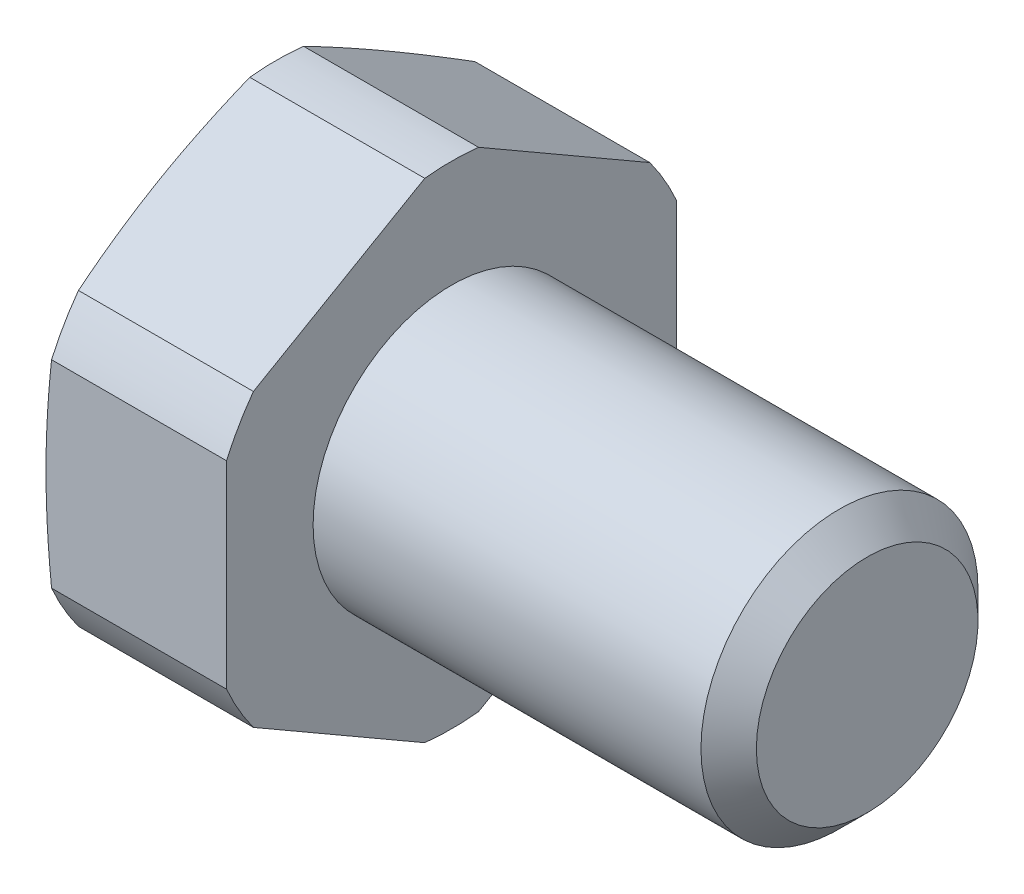
SolidWorks part; units mm, degrees
material "AISI 1020"
ref_plane "Спереди" through (0, 0, 0) normal (0, 0, 1) x (1, 0, 0)
ref_plane "Сверху" through (0, 0, 0) normal (0, 1, 0) x (1, 0, 0)
ref_plane "Справа" through (0, 0, 0) normal (1, 0, 0) x (0, 0, -1)
sketch "Эскиз1" plane through (0, 0, 0) normal (0, 0, 1) x (1, 0, 0)
  line L0 (-1000, 0) -> (49000, 0) construction
  line L1 (-5.3, 0) -> (-5.3, 6.175)
  line L2 (-5.3, 6.175) -> (-5.0521, 7.1)
  line L3 (-5.0521, 7.1) -> (0, 7.1)
  line L4 (0, 7.1) -> (0, 4)
  line L5 (0, 4) -> (11.2, 4)
  line L6 (12, 3.2) -> (12, 0)
  line L7 (12, 4) -> (12.625, 5.0825) construction
  line L8 (12.625, 5.0825) -> (13.25, 4) construction
  line L9 (13.25, 4) -> (12, 4) construction
  line L10 (12.625, 5.0825) -> (12.625, 4) construction
  line L11 (12.625, 5.0825) -> (0.625, 5.0825) construction
  line L12 (11.2, 4) -> (12, 3.2)
  line L13 (12, 4) -> (11.6, 3.6) construction
  line L14 (-5.3, 6.175) -> (-18.3, 6.175) construction
  line L15 (-5.3, 0) -> (12, 0)
  dimension "D2" = 15
revolve "Повернуть1" add sketch "Эскиз1" angle 360 about L0
cosmetic thread "Условное изображение резьбы1" parameters "D1"=12, "D2"=5.8349
sketch "Эскиз2" plane through (-5.3, 0, 0) normal (-1, 0, 0) x (0, 0, 1)
  line L1 (0, 7.5056) -> (-6.5, 3.7528)
  line L2 (-6.5, 3.7528) -> (-6.5, -3.7528)
  line L3 (-6.5, -3.7528) -> (0, -7.5056)
  line L4 (0, -7.5056) -> (6.5, -3.7528)
  line L5 (6.5, -3.7528) -> (6.5, 3.7528)
  line L6 (6.5, 3.7528) -> (0, 7.5056)
  circle A0 centre (0, 0) radius 6.5 construction
extrude "Вырез-Вытянуть1" cut sketch "Эскиз2" against normal up to surface (17.3 mm away) flip side to cut up to face at (12, 0, 3.2)
equation "\"D1@Эскиз1\"=\"_d_@Эскиз1\"/10"
equation "\"D@Эскиз1\"=\"S_@Эскиз1\"*0.95"
equation "\"D1@Эскиз2\"=\"S_@Эскиз1\""
equation "\"D1@Условное изображение резьбы1\"=\"b_@Эскиз1\""
equation "\"D2@Условное изображение резьбы1\"=\"_d_@Эскиз1\"-\"dr@Эскиз1\"*2"
